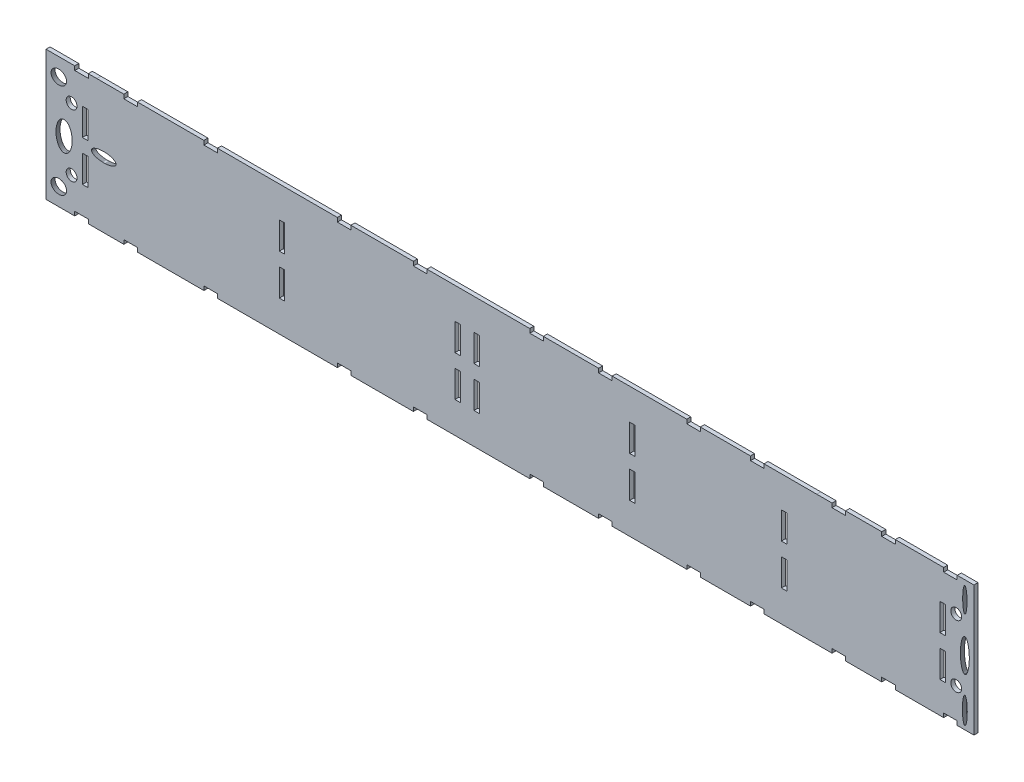
SolidWorks part; units mm, degrees
ref_plane "前视基准面" through (0, 0, 0) normal (0, 0, 1) x (1, 0, 0)
ref_plane "上视基准面" through (0, 0, 0) normal (0, 1, 0) x (1, 0, 0)
ref_plane "右视基准面" through (0, 0, 0) normal (1, 0, 0) x (0, 0, -1)
sketch "Model" plane through (0, 0, 0) normal (0, 0, 1) x (1, 0, 0)
  line L0 (338.2853, 1.7237) -> (348.2467, 1.7237)
  line L1 (353.2467, 1.7237) -> (377.8003, 1.7237)
  line L2 (382.8003, 1.7237) -> (412.5238, 1.7237)
  line L3 (412.5238, 49.7237) -> (382.8003, 49.7237)
  line L4 (377.8003, 49.7237) -> (353.2467, 49.7237)
  line L5 (348.2467, 49.7237) -> (338.2853, 49.7237)
  line L6 (405.6201, 38.2237) -> (407.6201, 38.2237)
  line L7 (405.6201, 38.2237) -> (405.6201, 28.2237)
  line L8 (407.6201, 28.2237) -> (405.6201, 28.2237)
  line L9 (405.6201, 23.2237) -> (405.6201, 13.2237)
  line L10 (407.6201, 13.2237) -> (405.6201, 13.2237)
  line L11 (407.6201, 38.2237) -> (407.6201, 28.2237)
  line L12 (407.6201, 23.2237) -> (407.6201, 13.2237)
  line L13 (405.6201, 23.2237) -> (407.6201, 23.2237)
  line L14 (348.2467, 49.7237) -> (348.2467, 48.2237)
  line L15 (348.2467, 48.2237) -> (353.2467, 48.2237)
  line L16 (353.2467, 49.7237) -> (353.2467, 48.2237)
  line L17 (348.2467, 1.7237) -> (348.2467, 3.2237)
  line L18 (348.2467, 3.2237) -> (353.2467, 3.2237)
  line L19 (353.2467, 1.7237) -> (353.2467, 3.2237)
  line L20 (377.8003, 49.7237) -> (377.8003, 48.2237)
  line L21 (377.8003, 48.2237) -> (382.8003, 48.2237)
  line L22 (382.8003, 49.7237) -> (382.8003, 48.2237)
  line L23 (382.8003, 1.7237) -> (382.8003, 3.2237)
  line L24 (382.8003, 3.2237) -> (377.8003, 3.2237)
  line L25 (377.8003, 1.7237) -> (377.8003, 3.2237)
  line L26 (412.5238, 1.7237) -> (427.0426, 1.7237)
  line L27 (427.0426, 49.7237) -> (412.5238, 49.7237)
  line L28 (427.0426, 49.7237) -> (427.0426, 48.2237)
  line L29 (427.0426, 48.2237) -> (432.0426, 48.2237)
  line L30 (432.0426, 49.7237) -> (432.0426, 48.2237)
  line L31 (432.0426, 1.7237) -> (432.0426, 3.2237)
  line L32 (432.0426, 3.2237) -> (427.0426, 3.2237)
  line L33 (427.0426, 1.7237) -> (427.0426, 3.2237)
  line L34 (432.0426, 1.7237) -> (436.5238, 1.7237)
  line L35 (432.0426, 49.7237) -> (436.5238, 49.7237)
  line L36 (598.2988, 49.7237) -> (603.9738, 49.7237)
  line L37 (609.6249, 1.7237) -> (598.2988, 1.7237)
  line L38 (646.1164, 49.7236) -> (632.9673, 49.7236)
  line L39 (627.9673, 49.7236) -> (614.6249, 49.7237)
  line L40 (609.6249, 49.7237) -> (603.9738, 49.7237)
  line L41 (614.6249, 1.7237) -> (627.9673, 1.7237)
  line L42 (632.9673, 1.7237) -> (646.1164, 1.7237)
  line L43 (627.9673, 1.7237) -> (627.9673, 3.2237)
  line L44 (627.9673, 3.2237) -> (632.9673, 3.2237)
  line L45 (632.9673, 1.7237) -> (632.9673, 3.2237)
  line L46 (609.6249, 1.7237) -> (609.6249, 3.2237)
  line L47 (609.6249, 3.2237) -> (614.6249, 3.2237)
  line L48 (614.6249, 1.7237) -> (614.6249, 3.2237)
  line L49 (632.9673, 49.7236) -> (632.9673, 48.2236)
  line L50 (632.9673, 48.2236) -> (627.9673, 48.2236)
  line L51 (627.9673, 49.7236) -> (627.9673, 48.2236)
  line L52 (614.6249, 49.7237) -> (614.6249, 48.2237)
  line L53 (614.6249, 48.2237) -> (609.6249, 48.2237)
  line L54 (609.6249, 49.7237) -> (609.6249, 48.2237)
  line L55 (548.2988, 1.7237) -> (556.0084, 1.7237)
  line L56 (561.0084, 1.7237) -> (579.5244, 1.7237)
  line L57 (584.5244, 1.7237) -> (598.2988, 1.7237)
  line L58 (598.2988, 49.7237) -> (584.5244, 49.7237)
  line L59 (579.5244, 49.7237) -> (561.0084, 49.7237)
  line L60 (590.9283, 38.2237) -> (592.9283, 38.2237)
  line L61 (590.9283, 38.2237) -> (590.9283, 28.2237)
  line L62 (592.9283, 28.2237) -> (590.9283, 28.2237)
  line L63 (590.9283, 23.2237) -> (590.9283, 13.2237)
  line L64 (592.9283, 13.2237) -> (590.9283, 13.2237)
  line L65 (592.9283, 38.2237) -> (592.9283, 28.2237)
  line L66 (592.9283, 23.2237) -> (592.9283, 13.2237)
  line L67 (590.9283, 23.2237) -> (592.9283, 23.2237)
  line L68 (579.5244, 49.7237) -> (579.5244, 48.2237)
  line L69 (579.5244, 48.2237) -> (584.5244, 48.2237)
  line L70 (584.5244, 49.7237) -> (584.5244, 48.2237)
  line L71 (556.0084, 49.7237) -> (556.0084, 48.2237)
  line L72 (556.0084, 48.2237) -> (561.0084, 48.2237)
  line L73 (561.0084, 49.7237) -> (561.0084, 48.2237)
  line L74 (584.5244, 1.7237) -> (584.5244, 3.2237)
  line L75 (584.5244, 3.2237) -> (579.5244, 3.2237)
  line L76 (579.5244, 1.7237) -> (579.5244, 3.2237)
  line L77 (561.0084, 1.7237) -> (561.0084, 3.2237)
  line L78 (561.0084, 3.2237) -> (556.0084, 3.2237)
  line L79 (556.0084, 1.7237) -> (556.0084, 3.2237)
  line L81 (556.0084, 49.7237) -> (548.2988, 49.7237)
  line L82 (460.1104, 1.7237) -> (484.6068, 1.7237)
  line L83 (484.6068, 1.7237) -> (498.0591, 1.7237)
  line L84 (503.0591, 1.7237) -> (523.4564, 1.7237)
  line L85 (528.4564, 1.7237) -> (548.2988, 1.7237)
  line L86 (548.2988, 49.7237) -> (528.4564, 49.7237)
  line L87 (523.4564, 49.7237) -> (503.0591, 49.7237)
  line L88 (498.0591, 49.7237) -> (484.6068, 49.7237)
  line L89 (484.6068, 49.7237) -> (460.1104, 49.7237)
  line L90 (470.4591, 38.2237) -> (472.4591, 38.2237)
  line L91 (470.4591, 38.2237) -> (470.4591, 28.2237)
  line L92 (472.4591, 28.2237) -> (470.4591, 28.2237)
  line L93 (470.4591, 23.2237) -> (470.4591, 13.2237)
  line L94 (472.4591, 13.2237) -> (470.4591, 13.2237)
  line L95 (472.4591, 38.2237) -> (472.4591, 28.2237)
  line L96 (472.4591, 23.2237) -> (472.4591, 13.2237)
  line L97 (470.4591, 23.2237) -> (472.4591, 23.2237)
  line L98 (477.4591, 38.2237) -> (479.4591, 38.2237)
  line L99 (477.4591, 38.2237) -> (477.4591, 28.2237)
  line L100 (479.4591, 28.2237) -> (477.4591, 28.2237)
  line L101 (477.4591, 23.2237) -> (477.4591, 13.2237)
  line L102 (479.4591, 13.2237) -> (477.4591, 13.2237)
  line L103 (479.4591, 38.2237) -> (479.4591, 28.2237)
  line L104 (479.4591, 23.2237) -> (479.4591, 13.2237)
  line L105 (477.4591, 23.2237) -> (479.4591, 23.2237)
  line L106 (534.9529, 38.2237) -> (536.9529, 38.2237)
  line L107 (534.9529, 38.2237) -> (534.9529, 28.2237)
  line L108 (536.9529, 28.2237) -> (534.9529, 28.2237)
  line L109 (534.9529, 23.2237) -> (534.9529, 13.2237)
  line L110 (536.9529, 13.2237) -> (534.9529, 13.2237)
  line L111 (536.9529, 38.2237) -> (536.9529, 28.2237)
  line L112 (536.9529, 23.2237) -> (536.9529, 13.2237)
  line L113 (534.9529, 23.2237) -> (536.9529, 23.2237)
  line L114 (523.4564, 49.7237) -> (523.4564, 48.2237)
  line L115 (523.4564, 48.2237) -> (528.4564, 48.2237)
  line L116 (528.4564, 49.7237) -> (528.4564, 48.2237)
  line L117 (498.0591, 49.7237) -> (498.0591, 48.2237)
  line L118 (498.0591, 48.2237) -> (503.0591, 48.2237)
  line L119 (503.0591, 49.7237) -> (503.0591, 48.2237)
  line L120 (455.1104, 49.7237) -> (455.1104, 48.2237)
  line L121 (455.1104, 48.2237) -> (460.1104, 48.2237)
  line L122 (460.1104, 49.7237) -> (460.1104, 48.2237)
  line L123 (528.4564, 1.7237) -> (528.4564, 3.2237)
  line L124 (528.4564, 3.2237) -> (523.4564, 3.2237)
  line L125 (523.4564, 1.7237) -> (523.4564, 3.2237)
  line L126 (503.0591, 1.7237) -> (503.0591, 3.2237)
  line L127 (503.0591, 3.2237) -> (498.0591, 3.2237)
  line L128 (498.0591, 1.7237) -> (498.0591, 3.2237)
  line L129 (460.1104, 1.7237) -> (460.1104, 3.2237)
  line L130 (460.1104, 3.2237) -> (455.1104, 3.2237)
  line L131 (455.1104, 1.7237) -> (455.1104, 3.2237)
  line L132 (436.5238, 49.7237) -> (455.1104, 49.7237)
  line L133 (436.5238, 1.7237) -> (455.1104, 1.7237)
  line L134 (319.5238, 49.7237) -> (330.1317, 49.7237)
  line L135 (335.1317, 49.7237) -> (338.2853, 49.7237)
  line L136 (338.2853, 1.7237) -> (335.1317, 1.7237)
  line L137 (330.1317, 1.7237) -> (319.5238, 1.7237)
  line L138 (319.5238, 1.7237) -> (319.5238, 49.7237)
  line L139 (332.9626, 13.2237) -> (334.9626, 13.2237)
  line L140 (332.9626, 13.2237) -> (332.9626, 23.2237)
  line L141 (334.9626, 23.2237) -> (332.9626, 23.2237)
  line L142 (332.9626, 28.2237) -> (332.9626, 38.2237)
  line L143 (334.9626, 38.2237) -> (332.9626, 38.2237)
  line L144 (334.9626, 13.2237) -> (334.9626, 23.2237)
  line L145 (334.9626, 28.2237) -> (334.9626, 38.2237)
  line L146 (332.9626, 28.2237) -> (334.9626, 28.2237)
  line L147 (330.1317, 1.7237) -> (330.1317, 3.2237)
  line L148 (330.1317, 3.2237) -> (335.1317, 3.2237)
  line L149 (335.1317, 1.7237) -> (335.1317, 3.2237)
  line L150 (330.1317, 49.7237) -> (330.1317, 48.2237)
  line L151 (330.1317, 48.2237) -> (335.1317, 48.2237)
  line L152 (335.1317, 49.7237) -> (335.1317, 48.2237)
  line L153 (661.9904, 1.7237) -> (655.8189, 1.7237)
  line L154 (650.8189, 1.7237) -> (646.1164, 1.7237)
  line L155 (646.1164, 49.7236) -> (650.8189, 49.7236)
  line L156 (655.8189, 49.7236) -> (661.9904, 49.7236)
  line L157 (661.9904, 49.7236) -> (661.9904, 1.7237)
  line L158 (649.4394, 38.2236) -> (651.4394, 38.2236)
  line L159 (649.4394, 38.2236) -> (649.4394, 28.2236)
  line L160 (651.4394, 28.2236) -> (649.4394, 28.2236)
  line L161 (649.4394, 23.2236) -> (649.4394, 13.2236)
  line L162 (651.4394, 13.2236) -> (649.4394, 13.2236)
  line L163 (651.4394, 38.2236) -> (651.4394, 28.2236)
  line L164 (651.4394, 23.2236) -> (651.4394, 13.2236)
  line L165 (649.4394, 23.2236) -> (651.4394, 23.2236)
  line L166 (650.8189, 49.7236) -> (650.8189, 48.2236)
  line L167 (650.8189, 48.2236) -> (655.8189, 48.2236)
  line L168 (655.8189, 49.7236) -> (655.8189, 48.2236)
  line L169 (655.8189, 1.7237) -> (655.8189, 3.2237)
  line L170 (655.8189, 3.2237) -> (650.8189, 3.2237)
  line L171 (650.8189, 1.7237) -> (650.8189, 3.2237)
  line L172 (345.3664, 25.8619) -> (345.3604, 25.7719)
  line L173 (345.3604, 25.7719) -> (345.3444, 25.6919)
  line L174 (345.3444, 25.6919) -> (345.3164, 25.6019)
  line L175 (345.3164, 25.6019) -> (345.2784, 25.5119)
  line L176 (345.2784, 25.5119) -> (345.2304, 25.4319)
  line L177 (345.2304, 25.4319) -> (345.1704, 25.3419)
  line L178 (345.1704, 25.3419) -> (345.1004, 25.2619)
  line L179 (345.1004, 25.2619) -> (345.0204, 25.1819)
  line L180 (345.0204, 25.1819) -> (344.9304, 25.1019)
  line L181 (344.9304, 25.1019) -> (344.8294, 25.0219)
  line L182 (344.8294, 25.0219) -> (344.7204, 24.9419)
  line L183 (344.7204, 24.9419) -> (344.6004, 24.8719)
  line L184 (344.6004, 24.8719) -> (344.4724, 24.8019)
  line L185 (344.4724, 24.8019) -> (344.3354, 24.7319)
  line L186 (344.3354, 24.7319) -> (344.1894, 24.6619)
  line L187 (344.1894, 24.6619) -> (344.0364, 24.6019)
  line L188 (344.0364, 24.6019) -> (343.8744, 24.5419)
  line L189 (343.8744, 24.5419) -> (343.7054, 24.4819)
  line L190 (343.7054, 24.4819) -> (343.5304, 24.4319)
  line L191 (343.5304, 24.4319) -> (343.3474, 24.3819)
  line L192 (343.3474, 24.3819) -> (343.1594, 24.3319)
  line L193 (343.1594, 24.3319) -> (342.9654, 24.2919)
  line L194 (342.9654, 24.2919) -> (342.7664, 24.2519)
  line L195 (342.7664, 24.2519) -> (342.5624, 24.2119)
  line L196 (342.5624, 24.2119) -> (342.3544, 24.1819)
  line L197 (342.3544, 24.1819) -> (342.1434, 24.1519)
  line L198 (342.1434, 24.1519) -> (341.9284, 24.1319)
  line L199 (341.9284, 24.1319) -> (341.7104, 24.1119)
  line L200 (341.7104, 24.1119) -> (341.4914, 24.1019)
  line L201 (341.4914, 24.1019) -> (341.2704, 24.0819)
  line L202 (341.2704, 24.0819) -> (341.0474, 24.0819)
  line L203 (341.0474, 24.0819) -> (340.8254, 24.0819)
  line L204 (340.8254, 24.0819) -> (340.6024, 24.0819)
  line L205 (340.6024, 24.0819) -> (340.3794, 24.0819)
  line L206 (340.3794, 24.0819) -> (340.1584, 24.1019)
  line L207 (340.1584, 24.1019) -> (339.9394, 24.1119)
  line L208 (339.9394, 24.1119) -> (339.7214, 24.1319)
  line L209 (339.7214, 24.1319) -> (339.5064, 24.1519)
  line L210 (339.5064, 24.1519) -> (339.2954, 24.1819)
  line L211 (339.2954, 24.1819) -> (339.0874, 24.2119)
  line L212 (339.0874, 24.2119) -> (338.8834, 24.2519)
  line L213 (338.8834, 24.2519) -> (338.6844, 24.2919)
  line L214 (338.6844, 24.2919) -> (338.4904, 24.3319)
  line L215 (338.4904, 24.3319) -> (338.3024, 24.3819)
  line L216 (338.3024, 24.3819) -> (338.1194, 24.4319)
  line L217 (338.1194, 24.4319) -> (337.9444, 24.4819)
  line L218 (337.9444, 24.4819) -> (337.7754, 24.5419)
  line L219 (337.7754, 24.5419) -> (337.6134, 24.6019)
  line L220 (337.6134, 24.6019) -> (337.4604, 24.6619)
  line L221 (337.4604, 24.6619) -> (337.3144, 24.7319)
  line L222 (337.3144, 24.7319) -> (337.1774, 24.8019)
  line L223 (337.1774, 24.8019) -> (337.0494, 24.8719)
  line L224 (337.0494, 24.8719) -> (336.9294, 24.9419)
  line L225 (336.9294, 24.9419) -> (336.8204, 25.0219)
  line L226 (336.8204, 25.0219) -> (336.7194, 25.1019)
  line L227 (336.7194, 25.1019) -> (336.6294, 25.1819)
  line L228 (336.6294, 25.1819) -> (336.5494, 25.2619)
  line L229 (336.5494, 25.2619) -> (336.4794, 25.3419)
  line L230 (336.4794, 25.3419) -> (336.4194, 25.4319)
  line L231 (336.4194, 25.4319) -> (336.3714, 25.5119)
  line L232 (336.3714, 25.5119) -> (336.3334, 25.6019)
  line L233 (336.3334, 25.6019) -> (336.3054, 25.6919)
  line L234 (336.3054, 25.6919) -> (336.2894, 25.7719)
  line L235 (336.2894, 25.7719) -> (336.2834, 25.8619)
  line L236 (336.2834, 25.8619) -> (336.2894, 25.9519)
  line L237 (336.2894, 25.9519) -> (336.3054, 26.0419)
  line L238 (336.3054, 26.0419) -> (336.3334, 26.1219)
  line L239 (336.3334, 26.1219) -> (336.3714, 26.2119)
  line L240 (336.3714, 26.2119) -> (336.4194, 26.2919)
  line L241 (336.4194, 26.2919) -> (336.4794, 26.3819)
  line L242 (336.4794, 26.3819) -> (336.5494, 26.4619)
  line L243 (336.5494, 26.4619) -> (336.6294, 26.5419)
  line L244 (336.6294, 26.5419) -> (336.7194, 26.6219)
  line L245 (336.7194, 26.6219) -> (336.8204, 26.7019)
  line L246 (336.8204, 26.7019) -> (336.9294, 26.7819)
  line L247 (336.9294, 26.7819) -> (337.0494, 26.8519)
  line L248 (337.0494, 26.8519) -> (337.1774, 26.9219)
  line L249 (337.1774, 26.9219) -> (337.3144, 26.9919)
  line L250 (337.3144, 26.9919) -> (337.4604, 27.0619)
  line L251 (337.4604, 27.0619) -> (337.6134, 27.1219)
  line L252 (337.6134, 27.1219) -> (337.7754, 27.1819)
  line L253 (337.7754, 27.1819) -> (337.9444, 27.2419)
  line L254 (337.9444, 27.2419) -> (338.1194, 27.2919)
  line L255 (338.1194, 27.2919) -> (338.3024, 27.3419)
  line L256 (338.3024, 27.3419) -> (338.4904, 27.3919)
  line L257 (338.4904, 27.3919) -> (338.6844, 27.4319)
  line L258 (338.6844, 27.4319) -> (338.8834, 27.4719)
  line L259 (338.8834, 27.4719) -> (339.0874, 27.5119)
  line L260 (339.0874, 27.5119) -> (339.2954, 27.5419)
  line L261 (339.2954, 27.5419) -> (339.5064, 27.5719)
  line L262 (339.5064, 27.5719) -> (339.7214, 27.5919)
  line L263 (339.7214, 27.5919) -> (339.9394, 27.6119)
  line L264 (339.9394, 27.6119) -> (340.1584, 27.6319)
  line L265 (340.1584, 27.6319) -> (340.3794, 27.6419)
  line L266 (340.3794, 27.6419) -> (340.6024, 27.6419)
  line L267 (340.6024, 27.6419) -> (340.8254, 27.6519)
  line L268 (340.8254, 27.6519) -> (341.0474, 27.6419)
  line L269 (341.0474, 27.6419) -> (341.2704, 27.6419)
  line L270 (341.2704, 27.6419) -> (341.4914, 27.6319)
  line L271 (341.4914, 27.6319) -> (341.7104, 27.6119)
  line L272 (341.7104, 27.6119) -> (341.9284, 27.5919)
  line L273 (341.9284, 27.5919) -> (342.1434, 27.5719)
  line L274 (342.1434, 27.5719) -> (342.3544, 27.5419)
  line L275 (342.3544, 27.5419) -> (342.5624, 27.5119)
  line L276 (342.5624, 27.5119) -> (342.7664, 27.4719)
  line L277 (342.7664, 27.4719) -> (342.9654, 27.4319)
  line L278 (342.9654, 27.4319) -> (343.1594, 27.3919)
  line L279 (343.1594, 27.3919) -> (343.3474, 27.3419)
  line L280 (343.3474, 27.3419) -> (343.5304, 27.2919)
  line L281 (343.5304, 27.2919) -> (343.7054, 27.2419)
  line L282 (343.7054, 27.2419) -> (343.8744, 27.1819)
  line L283 (343.8744, 27.1819) -> (344.0364, 27.1219)
  line L284 (344.0364, 27.1219) -> (344.1894, 27.0619)
  line L285 (344.1894, 27.0619) -> (344.3354, 26.9919)
  line L286 (344.3354, 26.9919) -> (344.4724, 26.9219)
  line L287 (344.4724, 26.9219) -> (344.6004, 26.8519)
  line L288 (344.6004, 26.8519) -> (344.7204, 26.7819)
  line L289 (344.7204, 26.7819) -> (344.8294, 26.7019)
  line L290 (344.8294, 26.7019) -> (344.9304, 26.6219)
  line L291 (344.9304, 26.6219) -> (345.0204, 26.5419)
  line L292 (345.0204, 26.5419) -> (345.1004, 26.4619)
  line L293 (345.1004, 26.4619) -> (345.1704, 26.3819)
  line L294 (345.1704, 26.3819) -> (345.2304, 26.2919)
  line L295 (345.2304, 26.2919) -> (345.2784, 26.2119)
  line L296 (345.2784, 26.2119) -> (345.3164, 26.1219)
  line L297 (345.3164, 26.1219) -> (345.3444, 26.0419)
  line L298 (345.3444, 26.0419) -> (345.3604, 25.9519)
  line L299 (345.3604, 25.9519) -> (345.3664, 25.8619)
  line L300 (326.1954, 19.9219) -> (326.0494, 19.9219)
  line L301 (326.0494, 19.9219) -> (325.9024, 19.9419)
  line L302 (325.9024, 19.9419) -> (325.7574, 19.9819)
  line L303 (325.7574, 19.9819) -> (325.6124, 20.0219)
  line L304 (325.6124, 20.0219) -> (325.4694, 20.0819)
  line L305 (325.4694, 20.0819) -> (325.3284, 20.1519)
  line L306 (325.3284, 20.1519) -> (325.1894, 20.2319)
  line L307 (325.1894, 20.2319) -> (325.0524, 20.3219)
  line L308 (325.0524, 20.3219) -> (324.9184, 20.4319)
  line L309 (324.9184, 20.4319) -> (324.7874, 20.5519)
  line L310 (324.7874, 20.5519) -> (324.6604, 20.6819)
  line L311 (324.6604, 20.6819) -> (324.5364, 20.8219)
  line L312 (324.5364, 20.8219) -> (324.4164, 20.9719)
  line L313 (324.4164, 20.9719) -> (324.3004, 21.1319)
  line L314 (324.3004, 21.1319) -> (324.1894, 21.3019)
  line L315 (324.1894, 21.3019) -> (324.0834, 21.4819)
  line L316 (324.0834, 21.4819) -> (323.9824, 21.6719)
  line L317 (323.9824, 21.6719) -> (323.8864, 21.8719)
  line L318 (323.8864, 21.8719) -> (323.7964, 22.0819)
  line L319 (323.7964, 22.0819) -> (323.7124, 22.2919)
  line L320 (323.7124, 22.2919) -> (323.6334, 22.5119)
  line L321 (323.6334, 22.5119) -> (323.5614, 22.7419)
  line L322 (323.5614, 22.7419) -> (323.4954, 22.9819)
  line L323 (323.4954, 22.9819) -> (323.4364, 23.2219)
  line L324 (323.4364, 23.2219) -> (323.3834, 23.4619)
  line L325 (323.3834, 23.4619) -> (323.3374, 23.7119)
  line L326 (323.3374, 23.7119) -> (323.2984, 23.9619)
  line L327 (323.2984, 23.9619) -> (323.2664, 24.2219)
  line L328 (323.2664, 24.2219) -> (323.2414, 24.4819)
  line L329 (323.2414, 24.4819) -> (323.2234, 24.7419)
  line L330 (323.2234, 24.7419) -> (323.2124, 25.0019)
  line L331 (323.2124, 25.0019) -> (323.2084, 25.2619)
  line L332 (323.2084, 25.2619) -> (323.2124, 25.5219)
  line L333 (323.2124, 25.5219) -> (323.2234, 25.7919)
  line L334 (323.2234, 25.7919) -> (323.2414, 26.0519)
  line L335 (323.2414, 26.0519) -> (323.2664, 26.3019)
  line L336 (323.2664, 26.3019) -> (323.2984, 26.5619)
  line L337 (323.2984, 26.5619) -> (323.3374, 26.8119)
  line L338 (323.3374, 26.8119) -> (323.3834, 27.0619)
  line L339 (323.3834, 27.0619) -> (323.4364, 27.3119)
  line L340 (323.4364, 27.3119) -> (323.4954, 27.5519)
  line L341 (323.4954, 27.5519) -> (323.5614, 27.7819)
  line L342 (323.5614, 27.7819) -> (323.6334, 28.0119)
  line L343 (323.6334, 28.0119) -> (323.7124, 28.2319)
  line L344 (323.7124, 28.2319) -> (323.7964, 28.4519)
  line L345 (323.7964, 28.4519) -> (323.8864, 28.6519)
  line L346 (323.8864, 28.6519) -> (323.9824, 28.8519)
  line L347 (323.9824, 28.8519) -> (324.0834, 29.0419)
  line L348 (324.0834, 29.0419) -> (324.1894, 29.2219)
  line L349 (324.1894, 29.2219) -> (324.3004, 29.3919)
  line L350 (324.3004, 29.3919) -> (324.4164, 29.5519)
  line L351 (324.4164, 29.5519) -> (324.5364, 29.7119)
  line L352 (324.5364, 29.7119) -> (324.6604, 29.8519)
  line L353 (324.6604, 29.8519) -> (324.7874, 29.9819)
  line L354 (324.7874, 29.9819) -> (324.9184, 30.0919)
  line L355 (324.9184, 30.0919) -> (325.0524, 30.2019)
  line L356 (325.0524, 30.2019) -> (325.1894, 30.2919)
  line L357 (325.1894, 30.2919) -> (325.3284, 30.3819)
  line L358 (325.3284, 30.3819) -> (325.4694, 30.4519)
  line L359 (325.4694, 30.4519) -> (325.6124, 30.5019)
  line L360 (325.6124, 30.5019) -> (325.7574, 30.5519)
  line L361 (325.7574, 30.5519) -> (325.9024, 30.5819)
  line L362 (325.9024, 30.5819) -> (326.0494, 30.6019)
  line L363 (326.0494, 30.6019) -> (326.1954, 30.6119)
  line L364 (326.1954, 30.6119) -> (326.3424, 30.6019)
  line L365 (326.3424, 30.6019) -> (326.4884, 30.5819)
  line L366 (326.4884, 30.5819) -> (326.6334, 30.5519)
  line L367 (326.6334, 30.5519) -> (326.7784, 30.5019)
  line L368 (326.7784, 30.5019) -> (326.9214, 30.4519)
  line L369 (326.9214, 30.4519) -> (327.0624, 30.3819)
  line L370 (327.0624, 30.3819) -> (327.2014, 30.2919)
  line L371 (327.2014, 30.2919) -> (327.3384, 30.2019)
  line L372 (327.3384, 30.2019) -> (327.4724, 30.0919)
  line L373 (327.4724, 30.0919) -> (327.6034, 29.9819)
  line L374 (327.6034, 29.9819) -> (327.7314, 29.8519)
  line L375 (327.7314, 29.8519) -> (327.8554, 29.7119)
  line L376 (327.8554, 29.7119) -> (327.9744, 29.5519)
  line L377 (327.9744, 29.5519) -> (328.0904, 29.3919)
  line L378 (328.0904, 29.3919) -> (328.2014, 29.2219)
  line L379 (328.2014, 29.2219) -> (328.3074, 29.0419)
  line L380 (328.3074, 29.0419) -> (328.4084, 28.8519)
  line L381 (328.4084, 28.8519) -> (328.5044, 28.6519)
  line L382 (328.5044, 28.6519) -> (328.5944, 28.4519)
  line L383 (328.5944, 28.4519) -> (328.6794, 28.2319)
  line L384 (328.6794, 28.2319) -> (328.7574, 28.0119)
  line L385 (328.7574, 28.0119) -> (328.8294, 27.7819)
  line L386 (328.8294, 27.7819) -> (328.8954, 27.5519)
  line L387 (328.8954, 27.5519) -> (328.9554, 27.3119)
  line L388 (328.9554, 27.3119) -> (329.0084, 27.0619)
  line L389 (329.0084, 27.0619) -> (329.0534, 26.8119)
  line L390 (329.0534, 26.8119) -> (329.0934, 26.5619)
  line L391 (329.0934, 26.5619) -> (329.1254, 26.3019)
  line L392 (329.1254, 26.3019) -> (329.1504, 26.0519)
  line L393 (329.1504, 26.0519) -> (329.1684, 25.7919)
  line L394 (329.1684, 25.7919) -> (329.1794, 25.5219)
  line L395 (329.1794, 25.5219) -> (329.1824, 25.2619)
  line L396 (329.1824, 25.2619) -> (329.1794, 25.0019)
  line L397 (329.1794, 25.0019) -> (329.1684, 24.7419)
  line L398 (329.1684, 24.7419) -> (329.1504, 24.4819)
  line L399 (329.1504, 24.4819) -> (329.1254, 24.2219)
  line L400 (329.1254, 24.2219) -> (329.0934, 23.9619)
  line L401 (329.0934, 23.9619) -> (329.0534, 23.7119)
  line L402 (329.0534, 23.7119) -> (329.0084, 23.4619)
  line L403 (329.0084, 23.4619) -> (328.9554, 23.2219)
  line L404 (328.9554, 23.2219) -> (328.8954, 22.9819)
  line L405 (328.8954, 22.9819) -> (328.8294, 22.7419)
  line L406 (328.8294, 22.7419) -> (328.7574, 22.5119)
  line L407 (328.7574, 22.5119) -> (328.6794, 22.2919)
  line L408 (328.6794, 22.2919) -> (328.5944, 22.0819)
  line L409 (328.5944, 22.0819) -> (328.5044, 21.8719)
  line L410 (328.5044, 21.8719) -> (328.4084, 21.6719)
  line L411 (328.4084, 21.6719) -> (328.3074, 21.4819)
  line L412 (328.3074, 21.4819) -> (328.2014, 21.3019)
  line L413 (328.2014, 21.3019) -> (328.0904, 21.1319)
  line L414 (328.0904, 21.1319) -> (327.9744, 20.9719)
  line L415 (327.9744, 20.9719) -> (327.8554, 20.8219)
  line L416 (327.8554, 20.8219) -> (327.7314, 20.6819)
  line L417 (327.7314, 20.6819) -> (327.6034, 20.5519)
  line L418 (327.6034, 20.5519) -> (327.4724, 20.4319)
  line L419 (327.4724, 20.4319) -> (327.3384, 20.3219)
  line L420 (327.3384, 20.3219) -> (327.2014, 20.2319)
  line L421 (327.2014, 20.2319) -> (327.0624, 20.1519)
  line L422 (327.0624, 20.1519) -> (326.9214, 20.0819)
  line L423 (326.9214, 20.0819) -> (326.7784, 20.0219)
  line L424 (326.7784, 20.0219) -> (326.6334, 19.9819)
  line L425 (326.6334, 19.9819) -> (326.4884, 19.9419)
  line L426 (326.4884, 19.9419) -> (326.3424, 19.9219)
  line L427 (326.3424, 19.9219) -> (326.1954, 19.9219)
  line L428 (321.3824, 8.2519) -> (321.3854, 8.3719)
  line L429 (321.3854, 8.3719) -> (321.3964, 8.5019)
  line L430 (321.3964, 8.5019) -> (321.4134, 8.6219)
  line L431 (321.4134, 8.6219) -> (321.4374, 8.7419)
  line L432 (321.4374, 8.7419) -> (321.4684, 8.8719)
  line L433 (321.4684, 8.8719) -> (321.5054, 8.9919)
  line L434 (321.5054, 8.9919) -> (321.5494, 9.1019)
  line L435 (321.5494, 9.1019) -> (321.6004, 9.2219)
  line L436 (321.6004, 9.2219) -> (321.6574, 9.3319)
  line L437 (321.6574, 9.3319) -> (321.7204, 9.4419)
  line L438 (321.7204, 9.4419) -> (321.7894, 9.5519)
  line L439 (321.7894, 9.5519) -> (321.8654, 9.6619)
  line L440 (321.8654, 9.6619) -> (321.9454, 9.7619)
  line L441 (321.9454, 9.7619) -> (322.0324, 9.8619)
  line L442 (322.0324, 9.8619) -> (322.1244, 9.9519)
  line L443 (322.1244, 9.9519) -> (322.2214, 10.0419)
  line L444 (322.2214, 10.0419) -> (322.3224, 10.1319)
  line L445 (322.3224, 10.1319) -> (322.4294, 10.2119)
  line L446 (322.4294, 10.2119) -> (322.5404, 10.2819)
  line L447 (322.5404, 10.2819) -> (322.6544, 10.3619)
  line L448 (322.6544, 10.3619) -> (322.7734, 10.4219)
  line L449 (322.7734, 10.4219) -> (322.8954, 10.4819)
  line L450 (322.8954, 10.4819) -> (323.0214, 10.5419)
  line L451 (323.0214, 10.5419) -> (323.1494, 10.5919)
  line L452 (323.1494, 10.5919) -> (323.2814, 10.6419)
  line L453 (323.2814, 10.6419) -> (323.4144, 10.6719)
  line L454 (323.4144, 10.6719) -> (323.5494, 10.7119)
  line L455 (323.5494, 10.7119) -> (323.6874, 10.7319)
  line L456 (323.6874, 10.7319) -> (323.8254, 10.7619)
  line L457 (323.8254, 10.7619) -> (323.9654, 10.7719)
  line L458 (323.9654, 10.7719) -> (324.1054, 10.7819)
  line L459 (324.1054, 10.7819) -> (324.2454, 10.7819)
  line L460 (324.2454, 10.7819) -> (324.3864, 10.7819)
  line L461 (324.3864, 10.7819) -> (324.5264, 10.7719)
  line L462 (324.5264, 10.7719) -> (324.6654, 10.7619)
  line L463 (324.6654, 10.7619) -> (324.8044, 10.7319)
  line L464 (324.8044, 10.7319) -> (324.9414, 10.7119)
  line L465 (324.9414, 10.7119) -> (325.0764, 10.6719)
  line L466 (325.0764, 10.6719) -> (325.2104, 10.6419)
  line L467 (325.2104, 10.6419) -> (325.3414, 10.5919)
  line L468 (325.3414, 10.5919) -> (325.4694, 10.5419)
  line L469 (325.4694, 10.5419) -> (325.5954, 10.4819)
  line L470 (325.5954, 10.4819) -> (325.7174, 10.4219)
  line L471 (325.7174, 10.4219) -> (325.8364, 10.3619)
  line L472 (325.8364, 10.3619) -> (325.9514, 10.2819)
  line L473 (325.9514, 10.2819) -> (326.0624, 10.2119)
  line L474 (326.0624, 10.2119) -> (326.1684, 10.1319)
  line L475 (326.1684, 10.1319) -> (326.2704, 10.0419)
  line L476 (326.2704, 10.0419) -> (326.3674, 9.9519)
  line L477 (326.3674, 9.9519) -> (326.4584, 9.8619)
  line L478 (326.4584, 9.8619) -> (326.5454, 9.7619)
  line L479 (326.5454, 9.7619) -> (326.6264, 9.6619)
  line L480 (326.6264, 9.6619) -> (326.7014, 9.5519)
  line L481 (326.7014, 9.5519) -> (326.7704, 9.4419)
  line L482 (326.7704, 9.4419) -> (326.8334, 9.3319)
  line L483 (326.8334, 9.3319) -> (326.8904, 9.2219)
  line L484 (326.8904, 9.2219) -> (326.9414, 9.1019)
  line L485 (326.9414, 9.1019) -> (326.9854, 8.9919)
  line L486 (326.9854, 8.9919) -> (327.0234, 8.8719)
  line L487 (327.0234, 8.8719) -> (327.0534, 8.7419)
  line L488 (327.0534, 8.7419) -> (327.0774, 8.6219)
  line L489 (327.0774, 8.6219) -> (327.0954, 8.5019)
  line L490 (327.0954, 8.5019) -> (327.1054, 8.3719)
  line L491 (327.1054, 8.3719) -> (327.1084, 8.2519)
  line L492 (327.1084, 8.2519) -> (327.1054, 8.1319)
  line L493 (327.1054, 8.1319) -> (327.0954, 8.0019)
  line L494 (327.0954, 8.0019) -> (327.0774, 7.8819)
  line L495 (327.0774, 7.8819) -> (327.0534, 7.7619)
  line L496 (327.0534, 7.7619) -> (327.0234, 7.6319)
  line L497 (327.0234, 7.6319) -> (326.9854, 7.5119)
  line L498 (326.9854, 7.5119) -> (326.9414, 7.4019)
  line L499 (326.9414, 7.4019) -> (326.8904, 7.2819)
  line L500 (326.8904, 7.2819) -> (326.8334, 7.1719)
  line L501 (326.8334, 7.1719) -> (326.7704, 7.0619)
  line L502 (326.7704, 7.0619) -> (326.7014, 6.9519)
  line L503 (326.7014, 6.9519) -> (326.6264, 6.8419)
  line L504 (326.6264, 6.8419) -> (326.5454, 6.7419)
  line L505 (326.5454, 6.7419) -> (326.4584, 6.6419)
  line L506 (326.4584, 6.6419) -> (326.3674, 6.5519)
  line L507 (326.3674, 6.5519) -> (326.2704, 6.4619)
  line L508 (326.2704, 6.4619) -> (326.1684, 6.3719)
  line L509 (326.1684, 6.3719) -> (326.0624, 6.2919)
  line L510 (326.0624, 6.2919) -> (325.9514, 6.2119)
  line L511 (325.9514, 6.2119) -> (325.8364, 6.1419)
  line L512 (325.8364, 6.1419) -> (325.7174, 6.0819)
  line L513 (325.7174, 6.0819) -> (325.5954, 6.0219)
  line L514 (325.5954, 6.0219) -> (325.4694, 5.9619)
  line L515 (325.4694, 5.9619) -> (325.3414, 5.9119)
  line L516 (325.3414, 5.9119) -> (325.2104, 5.8619)
  line L517 (325.2104, 5.8619) -> (325.0764, 5.8319)
  line L518 (325.0764, 5.8319) -> (324.9414, 5.7919)
  line L519 (324.9414, 5.7919) -> (324.8044, 5.7619)
  line L520 (324.8044, 5.7619) -> (324.6654, 5.7419)
  line L521 (324.6654, 5.7419) -> (324.5264, 5.7319)
  line L522 (324.5264, 5.7319) -> (324.3864, 5.7219)
  line L523 (324.3864, 5.7219) -> (324.2454, 5.7219)
  line L524 (324.2454, 5.7219) -> (324.1054, 5.7219)
  line L525 (324.1054, 5.7219) -> (323.9654, 5.7319)
  line L526 (323.9654, 5.7319) -> (323.8254, 5.7419)
  line L527 (323.8254, 5.7419) -> (323.6874, 5.7619)
  line L528 (323.6874, 5.7619) -> (323.5494, 5.7919)
  line L529 (323.5494, 5.7919) -> (323.4144, 5.8319)
  line L530 (323.4144, 5.8319) -> (323.2814, 5.8619)
  line L531 (323.2814, 5.8619) -> (323.1494, 5.9119)
  line L532 (323.1494, 5.9119) -> (323.0214, 5.9619)
  line L533 (323.0214, 5.9619) -> (322.8954, 6.0219)
  line L534 (322.8954, 6.0219) -> (322.7734, 6.0819)
  line L535 (322.7734, 6.0819) -> (322.6544, 6.1419)
  line L536 (322.6544, 6.1419) -> (322.5404, 6.2119)
  line L537 (322.5404, 6.2119) -> (322.4294, 6.2919)
  line L538 (322.4294, 6.2919) -> (322.3224, 6.3719)
  line L539 (322.3224, 6.3719) -> (322.2214, 6.4619)
  line L540 (322.2214, 6.4619) -> (322.1244, 6.5519)
  line L541 (322.1244, 6.5519) -> (322.0324, 6.6419)
  line L542 (322.0324, 6.6419) -> (321.9454, 6.7419)
  line L543 (321.9454, 6.7419) -> (321.8654, 6.8419)
  line L544 (321.8654, 6.8419) -> (321.7894, 6.9519)
  line L545 (321.7894, 6.9519) -> (321.7204, 7.0619)
  line L546 (321.7204, 7.0619) -> (321.6574, 7.1719)
  line L547 (321.6574, 7.1719) -> (321.6004, 7.2819)
  line L548 (321.6004, 7.2819) -> (321.5494, 7.4019)
  line L549 (321.5494, 7.4019) -> (321.5054, 7.5119)
  line L550 (321.5054, 7.5119) -> (321.4684, 7.6319)
  line L551 (321.4684, 7.6319) -> (321.4374, 7.7619)
  line L552 (321.4374, 7.7619) -> (321.4134, 7.8819)
  line L553 (321.4134, 7.8819) -> (321.3964, 8.0019)
  line L554 (321.3964, 8.0019) -> (321.3854, 8.1319)
  line L555 (321.3854, 8.1319) -> (321.3824, 8.2519)
  line L556 (321.3824, 43.1919) -> (321.3854, 43.0719)
  line L557 (321.3854, 43.0719) -> (321.3964, 42.9519)
  line L558 (321.3964, 42.9519) -> (321.4134, 42.8219)
  line L559 (321.4134, 42.8219) -> (321.4374, 42.7019)
  line L560 (321.4374, 42.7019) -> (321.4684, 42.5819)
  line L561 (321.4684, 42.5819) -> (321.5054, 42.4619)
  line L562 (321.5054, 42.4619) -> (321.5494, 42.3419)
  line L563 (321.5494, 42.3419) -> (321.6004, 42.2219)
  line L564 (321.6004, 42.2219) -> (321.6574, 42.1119)
  line L565 (321.6574, 42.1119) -> (321.7204, 42.0019)
  line L566 (321.7204, 42.0019) -> (321.7894, 41.8919)
  line L567 (321.7894, 41.8919) -> (321.8654, 41.7919)
  line L568 (321.8654, 41.7919) -> (321.9454, 41.6819)
  line L569 (321.9454, 41.6819) -> (322.0324, 41.5919)
  line L570 (322.0324, 41.5919) -> (322.1244, 41.4919)
  line L571 (322.1244, 41.4919) -> (322.2214, 41.4019)
  line L572 (322.2214, 41.4019) -> (322.3224, 41.3219)
  line L573 (322.3224, 41.3219) -> (322.4294, 41.2419)
  line L574 (322.4294, 41.2419) -> (322.5404, 41.1619)
  line L575 (322.5404, 41.1619) -> (322.6554, 41.0919)
  line L576 (322.6554, 41.0919) -> (322.7734, 41.0219)
  line L577 (322.7734, 41.0219) -> (322.8964, 40.9619)
  line L578 (322.8964, 40.9619) -> (323.0214, 40.9019)
  line L579 (323.0214, 40.9019) -> (323.1504, 40.8519)
  line L580 (323.1504, 40.8519) -> (323.2814, 40.8119)
  line L581 (323.2814, 40.8119) -> (323.4144, 40.7719)
  line L582 (323.4144, 40.7719) -> (323.5504, 40.7419)
  line L583 (323.5504, 40.7419) -> (323.6874, 40.7119)
  line L584 (323.6874, 40.7119) -> (323.8254, 40.6919)
  line L585 (323.8254, 40.6919) -> (323.9654, 40.6719)
  line L586 (323.9654, 40.6719) -> (324.1054, 40.6619)
  line L587 (324.1054, 40.6619) -> (324.2454, 40.6619)
  line L588 (324.2454, 40.6619) -> (324.3864, 40.6619)
  line L589 (324.3864, 40.6619) -> (324.5264, 40.6719)
  line L590 (324.5264, 40.6719) -> (324.6654, 40.6919)
  line L591 (324.6654, 40.6919) -> (324.8044, 40.7119)
  line L592 (324.8044, 40.7119) -> (324.9414, 40.7419)
  line L593 (324.9414, 40.7419) -> (325.0764, 40.7719)
  line L594 (325.0764, 40.7719) -> (325.2104, 40.8119)
  line L595 (325.2104, 40.8119) -> (325.3414, 40.8519)
  line L596 (325.3414, 40.8519) -> (325.4694, 40.9019)
  line L597 (325.4694, 40.9019) -> (325.5954, 40.9619)
  line L598 (325.5954, 40.9619) -> (325.7174, 41.0219)
  line L599 (325.7174, 41.0219) -> (325.8364, 41.0919)
  line L600 (325.8364, 41.0919) -> (325.9514, 41.1619)
  line L601 (325.9514, 41.1619) -> (326.0624, 41.2419)
  line L602 (326.0624, 41.2419) -> (326.1684, 41.3219)
  line L603 (326.1684, 41.3219) -> (326.2704, 41.4019)
  line L604 (326.2704, 41.4019) -> (326.3674, 41.4919)
  line L605 (326.3674, 41.4919) -> (326.4584, 41.5919)
  line L606 (326.4584, 41.5919) -> (326.5454, 41.6819)
  line L607 (326.5454, 41.6819) -> (326.6264, 41.7919)
  line L608 (326.6264, 41.7919) -> (326.7014, 41.8919)
  line L609 (326.7014, 41.8919) -> (326.7704, 42.0019)
  line L610 (326.7704, 42.0019) -> (326.8334, 42.1119)
  line L611 (326.8334, 42.1119) -> (326.8904, 42.2219)
  line L612 (326.8904, 42.2219) -> (326.9414, 42.3419)
  line L613 (326.9414, 42.3419) -> (326.9854, 42.4619)
  line L614 (326.9854, 42.4619) -> (327.0234, 42.5819)
  line L615 (327.0234, 42.5819) -> (327.0534, 42.7019)
  line L616 (327.0534, 42.7019) -> (327.0774, 42.8219)
  line L617 (327.0774, 42.8219) -> (327.0954, 42.9519)
  line L618 (327.0954, 42.9519) -> (327.1054, 43.0719)
  line L619 (327.1054, 43.0719) -> (327.1084, 43.1919)
  line L620 (327.1084, 43.1919) -> (327.1054, 43.3219)
  line L621 (327.1054, 43.3219) -> (327.0954, 43.4419)
  line L622 (327.0954, 43.4419) -> (327.0774, 43.5719)
  line L623 (327.0774, 43.5719) -> (327.0534, 43.6919)
  line L624 (327.0534, 43.6919) -> (327.0234, 43.8119)
  line L625 (327.0234, 43.8119) -> (326.9854, 43.9319)
  line L626 (326.9854, 43.9319) -> (326.9414, 44.0519)
  line L627 (326.9414, 44.0519) -> (326.8904, 44.1619)
  line L628 (326.8904, 44.1619) -> (326.8334, 44.2819)
  line L629 (326.8334, 44.2819) -> (326.7704, 44.3919)
  line L630 (326.7704, 44.3919) -> (326.7014, 44.5019)
  line L631 (326.7014, 44.5019) -> (326.6264, 44.6019)
  line L632 (326.6264, 44.6019) -> (326.5454, 44.7019)
  line L633 (326.5454, 44.7019) -> (326.4584, 44.8019)
  line L634 (326.4584, 44.8019) -> (326.3674, 44.9019)
  line L635 (326.3674, 44.9019) -> (326.2704, 44.9919)
  line L636 (326.2704, 44.9919) -> (326.1684, 45.0719)
  line L637 (326.1684, 45.0719) -> (326.0624, 45.1519)
  line L638 (326.0624, 45.1519) -> (325.9514, 45.2319)
  line L639 (325.9514, 45.2319) -> (325.8364, 45.3019)
  line L640 (325.8364, 45.3019) -> (325.7174, 45.3719)
  line L641 (325.7174, 45.3719) -> (325.5954, 45.4319)
  line L642 (325.5954, 45.4319) -> (325.4694, 45.4819)
  line L643 (325.4694, 45.4819) -> (325.3414, 45.5319)
  line L644 (325.3414, 45.5319) -> (325.2104, 45.5819)
  line L645 (325.2104, 45.5819) -> (325.0764, 45.6219)
  line L646 (325.0764, 45.6219) -> (324.9414, 45.6519)
  line L647 (324.9414, 45.6519) -> (324.8044, 45.6819)
  line L648 (324.8044, 45.6819) -> (324.6654, 45.7019)
  line L649 (324.6654, 45.7019) -> (324.5264, 45.7219)
  line L650 (324.5264, 45.7219) -> (324.3864, 45.7219)
  line L651 (324.3864, 45.7219) -> (324.2454, 45.7319)
  line L652 (324.2454, 45.7319) -> (324.1054, 45.7219)
  line L653 (324.1054, 45.7219) -> (323.9654, 45.7219)
  line L654 (323.9654, 45.7219) -> (323.8254, 45.7019)
  line L655 (323.8254, 45.7019) -> (323.6874, 45.6819)
  line L656 (323.6874, 45.6819) -> (323.5504, 45.6519)
  line L657 (323.5504, 45.6519) -> (323.4144, 45.6219)
  line L658 (323.4144, 45.6219) -> (323.2814, 45.5819)
  line L659 (323.2814, 45.5819) -> (323.1504, 45.5319)
  line L660 (323.1504, 45.5319) -> (323.0214, 45.4819)
  line L661 (323.0214, 45.4819) -> (322.8964, 45.4319)
  line L662 (322.8964, 45.4319) -> (322.7734, 45.3719)
  line L663 (322.7734, 45.3719) -> (322.6554, 45.3019)
  line L664 (322.6554, 45.3019) -> (322.5404, 45.2319)
  line L665 (322.5404, 45.2319) -> (322.4294, 45.1519)
  line L666 (322.4294, 45.1519) -> (322.3224, 45.0719)
  line L667 (322.3224, 45.0719) -> (322.2214, 44.9919)
  line L668 (322.2214, 44.9919) -> (322.1244, 44.9019)
  line L669 (322.1244, 44.9019) -> (322.0324, 44.8019)
  line L670 (322.0324, 44.8019) -> (321.9454, 44.7019)
  line L671 (321.9454, 44.7019) -> (321.8654, 44.6019)
  line L672 (321.8654, 44.6019) -> (321.7894, 44.5019)
  line L673 (321.7894, 44.5019) -> (321.7204, 44.3919)
  line L674 (321.7204, 44.3919) -> (321.6574, 44.2819)
  line L675 (321.6574, 44.2819) -> (321.6004, 44.1619)
  line L676 (321.6004, 44.1619) -> (321.5494, 44.0519)
  line L677 (321.5494, 44.0519) -> (321.5054, 43.9319)
  line L678 (321.5054, 43.9319) -> (321.4684, 43.8119)
  line L679 (321.4684, 43.8119) -> (321.4374, 43.6919)
  line L680 (321.4374, 43.6919) -> (321.4134, 43.5719)
  line L681 (321.4134, 43.5719) -> (321.3964, 43.4419)
  line L682 (321.3964, 43.4419) -> (321.3854, 43.3219)
  line L683 (321.3854, 43.3219) -> (321.3824, 43.1919)
  line L684 (658.6321, 31.5127) -> (658.5521, 31.5127)
  line L685 (658.5521, 31.5127) -> (658.4711, 31.4927)
  line L686 (658.4711, 31.4927) -> (658.3911, 31.4527)
  line L687 (658.3911, 31.4527) -> (658.3121, 31.4027)
  line L688 (658.3121, 31.4027) -> (658.2331, 31.3327)
  line L689 (658.2331, 31.3327) -> (658.1561, 31.2527)
  line L690 (658.1561, 31.2527) -> (658.0791, 31.1627)
  line L691 (658.0791, 31.1627) -> (658.0041, 31.0627)
  line L692 (658.0041, 31.0627) -> (657.9311, 30.9327)
  line L693 (657.9311, 30.9327) -> (657.8591, 30.8027)
  line L694 (657.8591, 30.8027) -> (657.7891, 30.6627)
  line L695 (657.7891, 30.6627) -> (657.7211, 30.5027)
  line L696 (657.7211, 30.5027) -> (657.6551, 30.3327)
  line L697 (657.6551, 30.3327) -> (657.5911, 30.1427)
  line L698 (657.5911, 30.1427) -> (657.5301, 29.9527)
  line L699 (657.5301, 29.9527) -> (657.4721, 29.7527)
  line L700 (657.4721, 29.7527) -> (657.4171, 29.5327)
  line L701 (657.4171, 29.5327) -> (657.3641, 29.3127)
  line L702 (657.3641, 29.3127) -> (657.3141, 29.0727)
  line L703 (657.3141, 29.0727) -> (657.2681, 28.8327)
  line L704 (657.2681, 28.8327) -> (657.2251, 28.5827)
  line L705 (657.2251, 28.5827) -> (657.1851, 28.3227)
  line L706 (657.1851, 28.3227) -> (657.1491, 28.0627)
  line L707 (657.1491, 28.0627) -> (657.1161, 27.7927)
  line L708 (657.1161, 27.7927) -> (657.0881, 27.5127)
  line L709 (657.0881, 27.5127) -> (657.0621, 27.2327)
  line L710 (657.0621, 27.2327) -> (657.0411, 26.9527)
  line L711 (657.0411, 26.9527) -> (657.0231, 26.6627)
  line L712 (657.0231, 26.6627) -> (657.0091, 26.3627)
  line L713 (657.0091, 26.3627) -> (657.0001, 26.0727)
  line L714 (657.0001, 26.0727) -> (656.9941, 25.7827)
  line L715 (656.9941, 25.7827) -> (656.9921, 25.4827)
  line L716 (656.9921, 25.4827) -> (656.9941, 25.1827)
  line L717 (656.9941, 25.1827) -> (657.0001, 24.8927)
  line L718 (657.0001, 24.8927) -> (657.0091, 24.5927)
  line L719 (657.0091, 24.5927) -> (657.0231, 24.3027)
  line L720 (657.0231, 24.3027) -> (657.0411, 24.0127)
  line L721 (657.0411, 24.0127) -> (657.0621, 23.7327)
  line L722 (657.0621, 23.7327) -> (657.0881, 23.4527)
  line L723 (657.0881, 23.4527) -> (657.1161, 23.1727)
  line L724 (657.1161, 23.1727) -> (657.1491, 22.9027)
  line L725 (657.1491, 22.9027) -> (657.1851, 22.6327)
  line L726 (657.1851, 22.6327) -> (657.2251, 22.3827)
  line L727 (657.2251, 22.3827) -> (657.2681, 22.1327)
  line L728 (657.2681, 22.1327) -> (657.3141, 21.8827)
  line L729 (657.3141, 21.8827) -> (657.3641, 21.6527)
  line L730 (657.3641, 21.6527) -> (657.4171, 21.4327)
  line L731 (657.4171, 21.4327) -> (657.4721, 21.2127)
  line L732 (657.4721, 21.2127) -> (657.5301, 21.0127)
  line L733 (657.5301, 21.0127) -> (657.5911, 20.8127)
  line L734 (657.5911, 20.8127) -> (657.6551, 20.6327)
  line L735 (657.6551, 20.6327) -> (657.7211, 20.4627)
  line L736 (657.7211, 20.4627) -> (657.7891, 20.3027)
  line L737 (657.7891, 20.3027) -> (657.8591, 20.1627)
  line L738 (657.8591, 20.1627) -> (657.9311, 20.0227)
  line L739 (657.9311, 20.0227) -> (658.0041, 19.9027)
  line L740 (658.0041, 19.9027) -> (658.0791, 19.8027)
  line L741 (658.0791, 19.8027) -> (658.1561, 19.7027)
  line L742 (658.1561, 19.7027) -> (658.2331, 19.6327)
  line L743 (658.2331, 19.6327) -> (658.3121, 19.5627)
  line L744 (658.3121, 19.5627) -> (658.3911, 19.5127)
  line L745 (658.3911, 19.5127) -> (658.4711, 19.4727)
  line L746 (658.4711, 19.4727) -> (658.5521, 19.4527)
  line L747 (658.5521, 19.4527) -> (658.6321, 19.4427)
  line L748 (658.6321, 19.4427) -> (658.7121, 19.4527)
  line L749 (658.7121, 19.4527) -> (658.7931, 19.4727)
  line L750 (658.7931, 19.4727) -> (658.8731, 19.5127)
  line L751 (658.8731, 19.5127) -> (658.9521, 19.5627)
  line L752 (658.9521, 19.5627) -> (659.0311, 19.6327)
  line L753 (659.0311, 19.6327) -> (659.1081, 19.7027)
  line L754 (659.1081, 19.7027) -> (659.1851, 19.8027)
  line L755 (659.1851, 19.8027) -> (659.2601, 19.9027)
  line L756 (659.2601, 19.9027) -> (659.3331, 20.0227)
  line L757 (659.3331, 20.0227) -> (659.4051, 20.1627)
  line L758 (659.4051, 20.1627) -> (659.4751, 20.3027)
  line L759 (659.4751, 20.3027) -> (659.5431, 20.4627)
  line L760 (659.5431, 20.4627) -> (659.6091, 20.6327)
  line L761 (659.6091, 20.6327) -> (659.6731, 20.8127)
  line L762 (659.6731, 20.8127) -> (659.7341, 21.0127)
  line L763 (659.7341, 21.0127) -> (659.7921, 21.2127)
  line L764 (659.7921, 21.2127) -> (659.8471, 21.4327)
  line L765 (659.8471, 21.4327) -> (659.9001, 21.6527)
  line L766 (659.9001, 21.6527) -> (659.9501, 21.8827)
  line L767 (659.9501, 21.8827) -> (659.9961, 22.1327)
  line L768 (659.9961, 22.1327) -> (660.0391, 22.3827)
  line L769 (660.0391, 22.3827) -> (660.0791, 22.6327)
  line L770 (660.0791, 22.6327) -> (660.1151, 22.9027)
  line L771 (660.1151, 22.9027) -> (660.1471, 23.1727)
  line L772 (660.1471, 23.1727) -> (660.1761, 23.4527)
  line L773 (660.1761, 23.4527) -> (660.2021, 23.7327)
  line L774 (660.2021, 23.7327) -> (660.2231, 24.0127)
  line L775 (660.2231, 24.0127) -> (660.2411, 24.3027)
  line L776 (660.2411, 24.3027) -> (660.2551, 24.5927)
  line L777 (660.2551, 24.5927) -> (660.2641, 24.8927)
  line L778 (660.2641, 24.8927) -> (660.2701, 25.1827)
  line L779 (660.2701, 25.1827) -> (660.2721, 25.4827)
  line L780 (660.2721, 25.4827) -> (660.2701, 25.7827)
  line L781 (660.2701, 25.7827) -> (660.2641, 26.0727)
  line L782 (660.2641, 26.0727) -> (660.2551, 26.3627)
  line L783 (660.2551, 26.3627) -> (660.2411, 26.6627)
  line L784 (660.2411, 26.6627) -> (660.2231, 26.9527)
  line L785 (660.2231, 26.9527) -> (660.2021, 27.2327)
  line L786 (660.2021, 27.2327) -> (660.1761, 27.5127)
  line L787 (660.1761, 27.5127) -> (660.1471, 27.7927)
  line L788 (660.1471, 27.7927) -> (660.1151, 28.0627)
  line L789 (660.1151, 28.0627) -> (660.0791, 28.3227)
  line L790 (660.0791, 28.3227) -> (660.0391, 28.5827)
  line L791 (660.0391, 28.5827) -> (659.9961, 28.8327)
  line L792 (659.9961, 28.8327) -> (659.9501, 29.0727)
  line L793 (659.9501, 29.0727) -> (659.9001, 29.3127)
  line L794 (659.9001, 29.3127) -> (659.8471, 29.5327)
  line L795 (659.8471, 29.5327) -> (659.7921, 29.7527)
  line L796 (659.7921, 29.7527) -> (659.7341, 29.9527)
  line L797 (659.7341, 29.9527) -> (659.6731, 30.1427)
  line L798 (659.6731, 30.1427) -> (659.6091, 30.3327)
  line L799 (659.6091, 30.3327) -> (659.5431, 30.5027)
  line L800 (659.5431, 30.5027) -> (659.4751, 30.6627)
  line L801 (659.4751, 30.6627) -> (659.4051, 30.8027)
  line L802 (659.4051, 30.8027) -> (659.3331, 30.9327)
  line L803 (659.3331, 30.9327) -> (659.2601, 31.0627)
  line L804 (659.2601, 31.0627) -> (659.1851, 31.1627)
  line L805 (659.1851, 31.1627) -> (659.1081, 31.2527)
  line L806 (659.1081, 31.2527) -> (659.0311, 31.3327)
  line L807 (659.0311, 31.3327) -> (658.9521, 31.4027)
  line L808 (658.9521, 31.4027) -> (658.8731, 31.4527)
  line L809 (658.8731, 31.4527) -> (658.7931, 31.4927)
  line L810 (658.7931, 31.4927) -> (658.7121, 31.5127)
  line L811 (658.7121, 31.5127) -> (658.6321, 31.5127)
  line L812 (658.6321, 12.8127) -> (658.5881, 12.8127)
  line L813 (658.5881, 12.8127) -> (658.5451, 12.7927)
  line L814 (658.5451, 12.7927) -> (658.5011, 12.7627)
  line L815 (658.5011, 12.7627) -> (658.4581, 12.7227)
  line L816 (658.4581, 12.7227) -> (658.4151, 12.6727)
  line L817 (658.4151, 12.6727) -> (658.3731, 12.6027)
  line L818 (658.3731, 12.6027) -> (658.3311, 12.5327)
  line L819 (658.3311, 12.5327) -> (658.2901, 12.4427)
  line L820 (658.2901, 12.4427) -> (658.2501, 12.3427)
  line L821 (658.2501, 12.3427) -> (658.2111, 12.2427)
  line L822 (658.2111, 12.2427) -> (658.1731, 12.1227)
  line L823 (658.1731, 12.1227) -> (658.1361, 11.9927)
  line L824 (658.1361, 11.9927) -> (658.1001, 11.8527)
  line L825 (658.1001, 11.8527) -> (658.0661, 11.7127)
  line L826 (658.0661, 11.7127) -> (658.0331, 11.5527)
  line L827 (658.0331, 11.5527) -> (658.0011, 11.3927)
  line L828 (658.0011, 11.3927) -> (657.9711, 11.2127)
  line L829 (657.9711, 11.2127) -> (657.9421, 11.0327)
  line L830 (657.9421, 11.0327) -> (657.9151, 10.8427)
  line L831 (657.9151, 10.8427) -> (657.8901, 10.6527)
  line L832 (657.8901, 10.6527) -> (657.8661, 10.4527)
  line L833 (657.8661, 10.4527) -> (657.8451, 10.2427)
  line L834 (657.8451, 10.2427) -> (657.8251, 10.0327)
  line L835 (657.8251, 10.0327) -> (657.8071, 9.8127)
  line L836 (657.8071, 9.8127) -> (657.7921, 9.5927)
  line L837 (657.7921, 9.5927) -> (657.7781, 9.3627)
  line L838 (657.7781, 9.3627) -> (657.7661, 9.1327)
  line L839 (657.7661, 9.1327) -> (657.7571, 8.9027)
  line L840 (657.7571, 8.9027) -> (657.7491, 8.6627)
  line L841 (657.7491, 8.6627) -> (657.7441, 8.4227)
  line L842 (657.7441, 8.4227) -> (657.7411, 8.1927)
  line L843 (657.7411, 8.1927) -> (657.7391, 7.9527)
  line L844 (657.7391, 7.9527) -> (657.7411, 7.7127)
  line L845 (657.7411, 7.7127) -> (657.7441, 7.4727)
  line L846 (657.7441, 7.4727) -> (657.7491, 7.2327)
  line L847 (657.7491, 7.2327) -> (657.7571, 7.0027)
  line L848 (657.7571, 7.0027) -> (657.7661, 6.7627)
  line L849 (657.7661, 6.7627) -> (657.7781, 6.5327)
  line L850 (657.7781, 6.5327) -> (657.7921, 6.3127)
  line L851 (657.7921, 6.3127) -> (657.8071, 6.0827)
  line L852 (657.8071, 6.0827) -> (657.8251, 5.8727)
  line L853 (657.8251, 5.8727) -> (657.8451, 5.6527)
  line L854 (657.8451, 5.6527) -> (657.8661, 5.4527)
  line L855 (657.8661, 5.4527) -> (657.8901, 5.2427)
  line L856 (657.8901, 5.2427) -> (657.9151, 5.0527)
  line L857 (657.9151, 5.0527) -> (657.9421, 4.8627)
  line L858 (657.9421, 4.8627) -> (657.9711, 4.6827)
  line L859 (657.9711, 4.6827) -> (658.0011, 4.5127)
  line L860 (658.0011, 4.5127) -> (658.0331, 4.3427)
  line L861 (658.0331, 4.3427) -> (658.0661, 4.1927)
  line L862 (658.0661, 4.1927) -> (658.1001, 4.0427)
  line L863 (658.1001, 4.0427) -> (658.1361, 3.9027)
  line L864 (658.1361, 3.9027) -> (658.1731, 3.7727)
  line L865 (658.1731, 3.7727) -> (658.2111, 3.6627)
  line L866 (658.2111, 3.6627) -> (658.2501, 3.5527)
  line L867 (658.2501, 3.5527) -> (658.2901, 3.4527)
  line L868 (658.2901, 3.4527) -> (658.3311, 3.3727)
  line L869 (658.3311, 3.3727) -> (658.3731, 3.2927)
  line L870 (658.3731, 3.2927) -> (658.4151, 3.2327)
  line L871 (658.4151, 3.2327) -> (658.4581, 3.1827)
  line L872 (658.4581, 3.1827) -> (658.5011, 3.1327)
  line L873 (658.5011, 3.1327) -> (658.5451, 3.1127)
  line L874 (658.5451, 3.1127) -> (658.5881, 3.0927)
  line L875 (658.5881, 3.0927) -> (658.6321, 3.0827)
  line L876 (658.6321, 3.0827) -> (658.6761, 3.0927)
  line L877 (658.6761, 3.0927) -> (658.7191, 3.1127)
  line L878 (658.7191, 3.1127) -> (658.7631, 3.1327)
  line L879 (658.7631, 3.1327) -> (658.8061, 3.1827)
  line L880 (658.8061, 3.1827) -> (658.8491, 3.2327)
  line L881 (658.8491, 3.2327) -> (658.8911, 3.2927)
  line L882 (658.8911, 3.2927) -> (658.9331, 3.3727)
  line L883 (658.9331, 3.3727) -> (658.9741, 3.4527)
  line L884 (658.9741, 3.4527) -> (659.0141, 3.5527)
  line L885 (659.0141, 3.5527) -> (659.0531, 3.6627)
  line L886 (659.0531, 3.6627) -> (659.0911, 3.7727)
  line L887 (659.0911, 3.7727) -> (659.1281, 3.9027)
  line L888 (659.1281, 3.9027) -> (659.1641, 4.0427)
  line L889 (659.1641, 4.0427) -> (659.1981, 4.1927)
  line L890 (659.1981, 4.1927) -> (659.2311, 4.3427)
  line L891 (659.2311, 4.3427) -> (659.2631, 4.5127)
  line L892 (659.2631, 4.5127) -> (659.2931, 4.6827)
  line L893 (659.2931, 4.6827) -> (659.3221, 4.8627)
  line L894 (659.3221, 4.8627) -> (659.3491, 5.0527)
  line L895 (659.3491, 5.0527) -> (659.3741, 5.2427)
  line L896 (659.3741, 5.2427) -> (659.3981, 5.4527)
  line L897 (659.3981, 5.4527) -> (659.4191, 5.6527)
  line L898 (659.4191, 5.6527) -> (659.4391, 5.8727)
  line L899 (659.4391, 5.8727) -> (659.4571, 6.0827)
  line L900 (659.4571, 6.0827) -> (659.4721, 6.3127)
  line L901 (659.4721, 6.3127) -> (659.4861, 6.5327)
  line L902 (659.4861, 6.5327) -> (659.4981, 6.7627)
  line L903 (659.4981, 6.7627) -> (659.5071, 7.0027)
  line L904 (659.5071, 7.0027) -> (659.5151, 7.2327)
  line L905 (659.5151, 7.2327) -> (659.5201, 7.4727)
  line L906 (659.5201, 7.4727) -> (659.5231, 7.7127)
  line L907 (659.5231, 7.7127) -> (659.5251, 7.9527)
  line L908 (659.5251, 7.9527) -> (659.5231, 8.1927)
  line L909 (659.5231, 8.1927) -> (659.5201, 8.4227)
  line L910 (659.5201, 8.4227) -> (659.5151, 8.6627)
  line L911 (659.5151, 8.6627) -> (659.5071, 8.9027)
  line L912 (659.5071, 8.9027) -> (659.4981, 9.1327)
  line L913 (659.4981, 9.1327) -> (659.4861, 9.3627)
  line L914 (659.4861, 9.3627) -> (659.4721, 9.5927)
  line L915 (659.4721, 9.5927) -> (659.4571, 9.8127)
  line L916 (659.4571, 9.8127) -> (659.4391, 10.0327)
  line L917 (659.4391, 10.0327) -> (659.4191, 10.2427)
  line L918 (659.4191, 10.2427) -> (659.3981, 10.4527)
  line L919 (659.3981, 10.4527) -> (659.3741, 10.6527)
  line L920 (659.3741, 10.6527) -> (659.3491, 10.8427)
  line L921 (659.3491, 10.8427) -> (659.3221, 11.0327)
  line L922 (659.3221, 11.0327) -> (659.2931, 11.2127)
  line L923 (659.2931, 11.2127) -> (659.2631, 11.3927)
  line L924 (659.2631, 11.3927) -> (659.2311, 11.5527)
  line L925 (659.2311, 11.5527) -> (659.1981, 11.7127)
  line L926 (659.1981, 11.7127) -> (659.1641, 11.8527)
  line L927 (659.1641, 11.8527) -> (659.1281, 11.9927)
  line L928 (659.1281, 11.9927) -> (659.0911, 12.1227)
  line L929 (659.0911, 12.1227) -> (659.0531, 12.2427)
  line L930 (659.0531, 12.2427) -> (659.0141, 12.3427)
  line L931 (659.0141, 12.3427) -> (658.9741, 12.4427)
  line L932 (658.9741, 12.4427) -> (658.9331, 12.5327)
  line L933 (658.9331, 12.5327) -> (658.8911, 12.6027)
  line L934 (658.8911, 12.6027) -> (658.8491, 12.6727)
  line L935 (658.8491, 12.6727) -> (658.8061, 12.7227)
  line L936 (658.8061, 12.7227) -> (658.7631, 12.7627)
  line L937 (658.7631, 12.7627) -> (658.7191, 12.7927)
  line L938 (658.7191, 12.7927) -> (658.6761, 12.8127)
  line L939 (658.6761, 12.8127) -> (658.6321, 12.8127)
  line L940 (658.6321, 47.8927) -> (658.5931, 47.8927)
  line L941 (658.5931, 47.8927) -> (658.5551, 47.8727)
  line L942 (658.5551, 47.8727) -> (658.5161, 47.8427)
  line L943 (658.5161, 47.8427) -> (658.4781, 47.8127)
  line L944 (658.4781, 47.8127) -> (658.4401, 47.7627)
  line L945 (658.4401, 47.7627) -> (658.4031, 47.7027)
  line L946 (658.4031, 47.7027) -> (658.3661, 47.6327)
  line L947 (658.3661, 47.6327) -> (658.3301, 47.5427)
  line L948 (658.3301, 47.5427) -> (658.2951, 47.4527)
  line L949 (658.2951, 47.4527) -> (658.2601, 47.3527)
  line L950 (658.2601, 47.3527) -> (658.2261, 47.2427)
  line L951 (658.2261, 47.2427) -> (658.1941, 47.1227)
  line L952 (658.1941, 47.1227) -> (658.1621, 46.9927)
  line L953 (658.1621, 46.9927) -> (658.1311, 46.8527)
  line L954 (658.1311, 46.8527) -> (658.1021, 46.7027)
  line L955 (658.1021, 46.7027) -> (658.0741, 46.5527)
  line L956 (658.0741, 46.5527) -> (658.0471, 46.3827)
  line L957 (658.0471, 46.3827) -> (658.0221, 46.2127)
  line L958 (658.0221, 46.2127) -> (657.9981, 46.0327)
  line L959 (657.9981, 46.0327) -> (657.9761, 45.8527)
  line L960 (657.9761, 45.8527) -> (657.9551, 45.6627)
  line L961 (657.9551, 45.6627) -> (657.9361, 45.4627)
  line L962 (657.9361, 45.4627) -> (657.9191, 45.2627)
  line L963 (657.9191, 45.2627) -> (657.9031, 45.0527)
  line L964 (657.9031, 45.0527) -> (657.8891, 44.8427)
  line L965 (657.8891, 44.8427) -> (657.8771, 44.6327)
  line L966 (657.8771, 44.6327) -> (657.8671, 44.4127)
  line L967 (657.8671, 44.4127) -> (657.8581, 44.1927)
  line L968 (657.8581, 44.1927) -> (657.8511, 43.9627)
  line L969 (657.8511, 43.9627) -> (657.8471, 43.7427)
  line L970 (657.8471, 43.7427) -> (657.8441, 43.5127)
  line L971 (657.8441, 43.5127) -> (657.8431, 43.2927)
  line L972 (657.8431, 43.2927) -> (657.8441, 43.0627)
  line L973 (657.8441, 43.0627) -> (657.8471, 42.8427)
  line L974 (657.8471, 42.8427) -> (657.8511, 42.6127)
  line L975 (657.8511, 42.6127) -> (657.8581, 42.3927)
  line L976 (657.8581, 42.3927) -> (657.8671, 42.1727)
  line L977 (657.8671, 42.1727) -> (657.8771, 41.9527)
  line L978 (657.8771, 41.9527) -> (657.8891, 41.7427)
  line L979 (657.8891, 41.7427) -> (657.9031, 41.5327)
  line L980 (657.9031, 41.5327) -> (657.9191, 41.3227)
  line L981 (657.9191, 41.3227) -> (657.9361, 41.1227)
  line L982 (657.9361, 41.1227) -> (657.9551, 40.9227)
  line L983 (657.9551, 40.9227) -> (657.9761, 40.7327)
  line L984 (657.9761, 40.7327) -> (657.9981, 40.5427)
  line L985 (657.9981, 40.5427) -> (658.0221, 40.3727)
  line L986 (658.0221, 40.3727) -> (658.0471, 40.1927)
  line L987 (658.0471, 40.1927) -> (658.0741, 40.0327)
  line L988 (658.0741, 40.0327) -> (658.1021, 39.8727)
  line L989 (658.1021, 39.8727) -> (658.1311, 39.7327)
  line L990 (658.1311, 39.7327) -> (658.1621, 39.5927)
  line L991 (658.1621, 39.5927) -> (658.1941, 39.4627)
  line L992 (658.1941, 39.4627) -> (658.2261, 39.3427)
  line L993 (658.2261, 39.3427) -> (658.2601, 39.2327)
  line L994 (658.2601, 39.2327) -> (658.2951, 39.1227)
  line L995 (658.2951, 39.1227) -> (658.3301, 39.0327)
  line L996 (658.3301, 39.0327) -> (658.3661, 38.9527)
  line L997 (658.3661, 38.9527) -> (658.4031, 38.8827)
  line L998 (658.4031, 38.8827) -> (658.4401, 38.8227)
  line L999 (658.4401, 38.8227) -> (658.4781, 38.7727)
  line L1000 (658.4781, 38.7727) -> (658.5161, 38.7327)
  line L1001 (658.5161, 38.7327) -> (658.5551, 38.7027)
  line L1002 (658.5551, 38.7027) -> (658.5931, 38.6927)
  line L1003 (658.5931, 38.6927) -> (658.6321, 38.6827)
  line L1004 (658.6321, 38.6827) -> (658.6711, 38.6927)
  line L1005 (658.6711, 38.6927) -> (658.7091, 38.7027)
  line L1006 (658.7091, 38.7027) -> (658.7481, 38.7327)
  line L1007 (658.7481, 38.7327) -> (658.7861, 38.7727)
  line L1008 (658.7861, 38.7727) -> (658.8241, 38.8227)
  line L1009 (658.8241, 38.8227) -> (658.8611, 38.8827)
  line L1010 (658.8611, 38.8827) -> (658.8981, 38.9527)
  line L1011 (658.8981, 38.9527) -> (658.9341, 39.0327)
  line L1012 (658.9341, 39.0327) -> (658.9691, 39.1227)
  line L1013 (658.9691, 39.1227) -> (659.0041, 39.2327)
  line L1014 (659.0041, 39.2327) -> (659.0381, 39.3427)
  line L1015 (659.0381, 39.3427) -> (659.0701, 39.4627)
  line L1016 (659.0701, 39.4627) -> (659.1021, 39.5927)
  line L1017 (659.1021, 39.5927) -> (659.1331, 39.7327)
  line L1018 (659.1331, 39.7327) -> (659.1621, 39.8727)
  line L1019 (659.1621, 39.8727) -> (659.1901, 40.0327)
  line L1020 (659.1901, 40.0327) -> (659.2171, 40.1927)
  line L1021 (659.2171, 40.1927) -> (659.2421, 40.3727)
  line L1022 (659.2421, 40.3727) -> (659.2661, 40.5427)
  line L1023 (659.2661, 40.5427) -> (659.2881, 40.7327)
  line L1024 (659.2881, 40.7327) -> (659.3091, 40.9227)
  line L1025 (659.3091, 40.9227) -> (659.3281, 41.1227)
  line L1026 (659.3281, 41.1227) -> (659.3451, 41.3227)
  line L1027 (659.3451, 41.3227) -> (659.3611, 41.5327)
  line L1028 (659.3611, 41.5327) -> (659.3751, 41.7427)
  line L1029 (659.3751, 41.7427) -> (659.3871, 41.9527)
  line L1030 (659.3871, 41.9527) -> (659.3971, 42.1727)
  line L1031 (659.3971, 42.1727) -> (659.4061, 42.3927)
  line L1032 (659.4061, 42.3927) -> (659.4131, 42.6127)
  line L1033 (659.4131, 42.6127) -> (659.4171, 42.8427)
  line L1034 (659.4171, 42.8427) -> (659.4201, 43.0627)
  line L1035 (659.4201, 43.0627) -> (659.4211, 43.2927)
  line L1036 (659.4211, 43.2927) -> (659.4201, 43.5127)
  line L1037 (659.4201, 43.5127) -> (659.4171, 43.7427)
  line L1038 (659.4171, 43.7427) -> (659.4131, 43.9627)
  line L1039 (659.4131, 43.9627) -> (659.4061, 44.1927)
  line L1040 (659.4061, 44.1927) -> (659.3971, 44.4127)
  line L1041 (659.3971, 44.4127) -> (659.3871, 44.6327)
  line L1042 (659.3871, 44.6327) -> (659.3751, 44.8427)
  line L1043 (659.3751, 44.8427) -> (659.3611, 45.0527)
  line L1044 (659.3611, 45.0527) -> (659.3451, 45.2627)
  line L1045 (659.3451, 45.2627) -> (659.3281, 45.4627)
  line L1046 (659.3281, 45.4627) -> (659.3091, 45.6627)
  line L1047 (659.3091, 45.6627) -> (659.2881, 45.8527)
  line L1048 (659.2881, 45.8527) -> (659.2661, 46.0327)
  line L1049 (659.2661, 46.0327) -> (659.2421, 46.2127)
  line L1050 (659.2421, 46.2127) -> (659.2171, 46.3827)
  line L1051 (659.2171, 46.3827) -> (659.1901, 46.5527)
  line L1052 (659.1901, 46.5527) -> (659.1621, 46.7027)
  line L1053 (659.1621, 46.7027) -> (659.1331, 46.8527)
  line L1054 (659.1331, 46.8527) -> (659.1021, 46.9927)
  line L1055 (659.1021, 46.9927) -> (659.0701, 47.1227)
  line L1056 (659.0701, 47.1227) -> (659.0381, 47.2427)
  line L1057 (659.0381, 47.2427) -> (659.0041, 47.3527)
  line L1058 (659.0041, 47.3527) -> (658.9691, 47.4527)
  line L1059 (658.9691, 47.4527) -> (658.9341, 47.5427)
  line L1060 (658.9341, 47.5427) -> (658.8981, 47.6327)
  line L1061 (658.8981, 47.6327) -> (658.8611, 47.7027)
  line L1062 (658.8611, 47.7027) -> (658.8241, 47.7627)
  line L1063 (658.8241, 47.7627) -> (658.7861, 47.8127)
  line L1064 (658.7861, 47.8127) -> (658.7481, 47.8427)
  line L1065 (658.7481, 47.8427) -> (658.7091, 47.8727)
  line L1066 (658.7091, 47.8727) -> (658.6711, 47.8927)
  line L1067 (658.6711, 47.8927) -> (658.6321, 47.8927)
  circle A0 centre (655.4386, 14.2237) radius 2
  circle A1 centre (655.4386, 37.2237) radius 2
  circle A2 centre (328.9631, 37.2237) radius 2
  circle A3 centre (328.9631, 14.2237) radius 2
extrude "凸台-拉伸1" add sketch "Model" along normal blind 1.5
